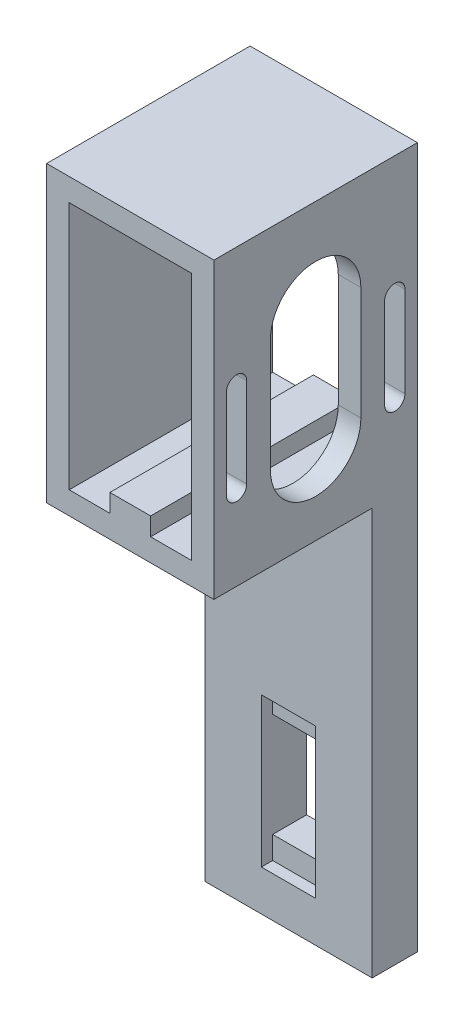
SolidWorks part; units mm, degrees
ref_plane "Plan de face" through (0, 0, 0) normal (0, 0, 1) x (1, 0, 0)
ref_plane "Plan de dessus" through (0, 0, 0) normal (0, 1, 0) x (1, 0, 0)
ref_plane "Plan de droite" through (0, 0, 0) normal (1, 0, 0) x (0, 0, -1)
sketch "Esquisse1" plane through (0, 0, 0) normal (0, 0, 1) x (1, 0, 0)
  line L0 (-40.1057, 31.5871) -> (-35.1057, 31.5871)
  line L2 (-40.1057, 31.5871) -> (-40.1057, -28.4129)
  line L3 (-40.1057, -28.4129) -> (-3.1057, -28.4129)
  line L4 (-3.1057, 31.5871) -> (-3.1057, -28.4129)
  line L5 (-35.1057, 31.5871) -> (-35.1057, -23.4129)
  line L6 (-35.1057, -23.4129) -> (-26.1057, -23.4129)
  line L7 (-26.1057, -23.4129) -> (-26.1057, -19.4129)
  line L8 (-26.1057, -19.4129) -> (-17.1057, -19.4129)
  line L9 (-17.1057, -19.4129) -> (-17.1057, -23.4129)
  line L10 (-17.1057, -23.4129) -> (-8.1057, -23.4129)
  line L11 (-8.1057, -23.4129) -> (-8.1057, 31.5871)
  line L12 (-8.1057, 31.5871) -> (-3.1057, 31.5871)
  dimension "D1" = 37
  dimension "D2" = 60
  dimension "D3" = 5
  dimension "D4" = 5
  dimension "D5" = 9
  dimension "D6" = 9
  dimension "D7" = 5
  dimension "D8" = 4
  dimension "D9" = 4
  dimension "D10" = 9
  dimension "D11" = 60
extrude "Boss.-Extru.1" add sketch "Esquisse1" along normal blind 45
sketch "Esquisse2" plane through (-3.1057, 0, 0) normal (1, 0, 0) x (0, 0, -1)
  line L0 (-22.5, 31.5871) -> (-22.5, -28.4129) construction
  line L1 (-45, 31.5871) -> (0, 31.5871) construction
  line L2 (-45, -28.4129) -> (0, -28.4129) construction
  line L3 (-22.5, 15.0871) -> (-22.5, -9.9129) construction
  line L4 (-12.5, 15.0871) -> (-12.5, -9.9129)
  line L5 (-32.5, 15.0871) -> (-32.5, -9.9129)
  line L6 (-53.101, 2.5871) -> (12.8547, 2.5871) construction
  line L7 (-40, 15.1582) -> (-40, -20.8265) construction
  line L10 (-40, 9.8775) -> (-40, -9.9129) construction
  line L11 (-5, 16.6338) -> (-5, -20.8265) construction
  line L12 (-37.75, 9.8775) -> (-37.75, -9.9129)
  line L13 (-42.25, 9.8775) -> (-42.25, -9.9129)
  line L14 (-37.75, -9.9129) -> (20.4864, -9.9129) construction
  line L15 (20.4864, -9.9129) -> (20.4864, 9.8775) construction
  line L16 (20.4864, 9.8775) -> (-68.9251, 9.8775) construction
  line L17 (-5, 9.8775) -> (-5, -10.1225) construction
  line L18 (-2.75, 9.8775) -> (-2.75, -10.1225)
  line L19 (-7.25, 9.8775) -> (-7.25, -10.1225)
  arc A0 (-12.5, 15.0871) -> (-32.5, 15.0871) centre (-22.5, 15.0871) ccw
  arc A1 (-32.5, -9.9129) -> (-12.5, -9.9129) centre (-22.5, -9.9129) ccw
  arc A4 (-37.75, 9.8775) -> (-42.25, 9.8775) centre (-40, 9.8775) ccw
  arc A5 (-42.25, -9.9129) -> (-37.75, -9.9129) centre (-40, -9.9129) ccw
  arc A6 (-2.75, 9.8775) -> (-7.25, 9.8775) centre (-5, 9.8775) ccw
  arc A7 (-7.25, -10.1225) -> (-2.75, -10.1225) centre (-5, -10.1225) ccw
  point P8 (-22.5, 2.5871)
  point P17 (-40, -0.0177)
  point P33 (-5, -0.1225)
  dimension "D1" = 20
  dimension "D3" = 16.5
  dimension "D2" = 25
  dimension "D4" = 35
  dimension "D5" = 5.25
  dimension "D6" = 4.5
  dimension "D7" = 4.5
  dimension "D8" = 5.25
extrude "Enlèv. mat.-Extru.1" cut sketch "Esquisse2" against normal up to surface (5 mm away) up to face at (-8.1057, 4.0871, 22.5)
sketch "Esquisse4" plane through (0, 31.5871, 0) normal (0, 1, 0) x (1, 0, 0)
  line L0 (-40.1057, -45) -> (-40.1057, 0) construction
  line L1 (-40.1057, 0) -> (-3.1057, 0)
  line L2 (-40.1057, 0) -> (-40.1057, -45)
  line L3 (-40.1057, -45) -> (-3.1057, -45)
  line L4 (-3.1057, 0) -> (-3.1057, -45)
extrude "Boss.-Extru.2" add sketch "Esquisse4" along normal blind 5
sketch "Esquisse5" plane through (0, -28.4129, 0) normal (0, -1, 0) x (1, 0, 0)
  line L0 (-3.1057, 45) -> (-3.1057, 0) construction
  line L1 (-40.1057, 0) -> (-3.1057, 0)
  line L2 (-40.1057, 0) -> (-40.1057, 10)
  line L3 (-40.1057, 10) -> (-3.1057, 10)
  line L4 (-3.1057, 0) -> (-3.1057, 10)
  dimension "D1" = 10
extrude "Boss.-Extru.3" add sketch "Esquisse5" along normal blind 90
sketch "Esquisse6" plane through (-40.1057, 0, 0) normal (-1, 0, 0) x (0, 0, 1)
  line L0 (45, -23.4129) -> (0, -23.4129) construction
  line L1 (45, 36.5871) -> (45, -28.4129) construction
  line L2 (0, 36.5871) -> (0, -118.4129) construction
  line L3 (45, -28.4129) -> (10, -28.4129) construction
  line L4 (15, -23.4129) -> (15, 3.3301) construction
  circle A0 centre (15, -18.4129) radius 1
  circle A1 centre (15, -8.9129) radius 1
  dimension "D2" = 2
  dimension "D5" = 2
  dimension "D1" = 5
  dimension "D3" = 5
  dimension "D4" = 9.5
  dimension "D6" = 15
extrude "Enlèv. mat.-Extru.2" cut sketch "Esquisse6" against normal blind 10
chamfer "Chanfrein2" distance 1 angle 45 2 edges at (-35.1057, -19.4129, 15) (-35.1057, -9.9129, 15)
sketch "Esquisse7" plane through (0, 0, 10) normal (0, 0, 1) x (1, 0, 0)
  line L0 (-21.6057, -28.4129) -> (-21.6057, -118.4129) construction
  line L1 (-3.1057, -28.4129) -> (-40.1057, -28.4129) construction
  line L2 (-3.1057, -118.4129) -> (-40.1057, -118.4129) construction
  line L3 (-27.6057, -104.4129) -> (-15.6057, -104.4129)
  line L4 (-40.1057, -118.4129) -> (-40.1057, -28.4129) construction
  line L5 (-40.1057, -98.4129) -> (-3.1057, -98.4129) construction
  line L6 (-3.1057, -118.4129) -> (-3.1057, -28.4129) construction
  line L7 (-15.6057, -104.4129) -> (-15.6057, -81.4129)
  line L8 (-15.6057, -81.4129) -> (-27.6057, -81.4129)
  line L9 (-27.6057, -81.4129) -> (-27.6057, -104.4129)
  point P15 (-21.6057, -104.4129)
  dimension "D1" = 70
  dimension "D2" = 12
  dimension "D3" = 23
  dimension "D4" = 6
extrude "Enlèv. mat.-Extru.3" cut sketch "Esquisse7" against normal blind 10
sketch "Esquisse8" plane through (0, 0, 10) normal (0, 0, 1) x (1, 0, 0)
  line L1 (-27.6057, -81.4129) -> (-15.6057, -81.4129)
  line L2 (-27.6057, -81.4129) -> (-27.6057, -76.4129)
  line L3 (-27.6057, -76.4129) -> (-15.6057, -76.4129)
  line L4 (-15.6057, -81.4129) -> (-15.6057, -76.4129)
  line L5 (-27.6057, -104.4129) -> (-15.6057, -104.4129)
  line L6 (-27.6057, -104.4129) -> (-27.6057, -109.4129)
  line L7 (-27.6057, -109.4129) -> (-15.6057, -109.4129)
  line L8 (-15.6057, -104.4129) -> (-15.6057, -109.4129)
  dimension "D1" = 12
  dimension "D2" = 12
  dimension "D3" = 5
  dimension "D4" = 5
extrude "Enlèv. mat.-Extru.4" cut sketch "Esquisse8" against normal blind 2.5
